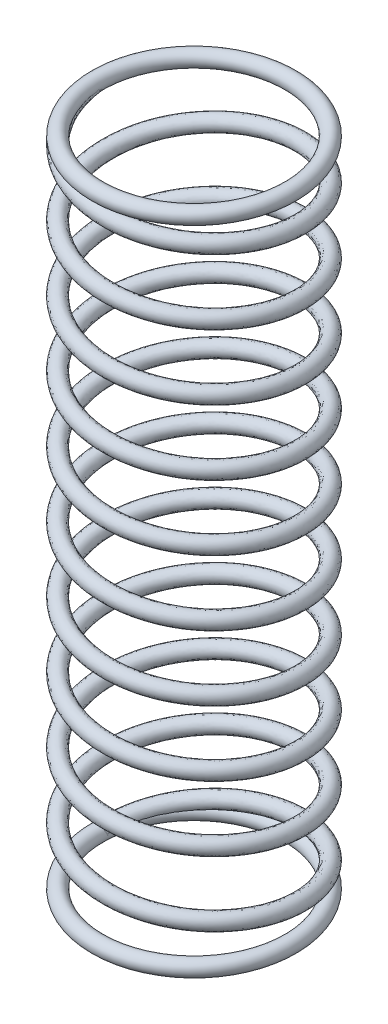
SolidWorks part; units mm, degrees
note: '?' marks a value the reader was unsure of.
ref_plane "Plan de face" through (0, 0, 0) normal (0, 0, 1) x (1, 0, 0)
ref_plane "Plan de dessus" through (0, 0, 0) normal (0, 1, 0) x (1, 0, 0)
ref_plane "Plan de droite" through (0, 0, 0) normal (1, 0, 0) x (0, 0, -1)
sketch "Esquisse1" plane through (0, 0, 0) normal (0, 1, 0) x (1, 0, 0)
  circle A0 centre (0, 0) radius 3.7
  dimension "D1" = 7.4
sketch "Esquisse16" plane through (0, 0, 0) normal (0, 1, 0) x (1, 0, 0)
  circle A2 centre (0, 0) radius 3.7
  circle A3 centre (0, 0) radius 3.7 construction
sweep "Balayage4" add path "Esquisse16" circular profile diameter 0.6 parameters "D3"=0.6
sketch "Esquisse59" plane through (0, 0, 0) normal (0, 1, 0) x (1, 0, 0)
  circle A0 centre (0, 0) radius 3.7
  circle A1 centre (0, 0) radius 3.7 construction
curve "Hélice/Spirale2" pitch 2.5 height 25 turns 10
sweep "Balayage5" add path "Hélice/Spirale2" circular profile diameter 0.6 parameters "D3"=0.6
ref_plane "Plan1" through (0, 25, 0) normal (0, 1, 0) x (1, 0, 0)
sketch "Esquisse68" plane through (0, 25, 0) normal (0, 1, 0) x (1, 0, 0)
  circle A0 centre (0, 0) radius 3.7
  circle A1 centre (0, 0) radius 3.7 construction
sweep "Balayage8" add path "Esquisse68" circular profile diameter 0.6 parameters "D3"=0.6
ref_axis "Axe1" through (0, 26.58, 0) along (0, -1, 0)?
equation "\"D1@Esquisse1\"=\"outer_diameter\"-\"wire_diameter\""
equation "\"wire_diameter\"= 0.6"
equation "\"D3@Balayage4\"=\"wire_diameter\""
equation "\"D3@Balayage5\"=\"wire_diameter\""
equation "\"D3@Balayage8\"=\"wire_diameter\""
equation "\"outer_diameter\"=8"
